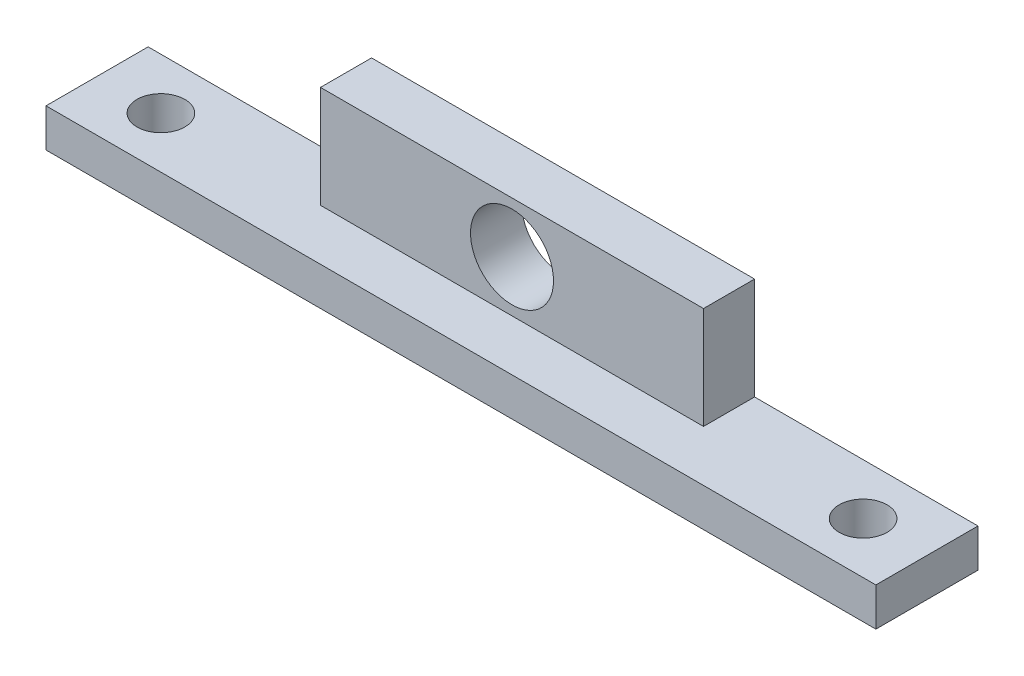
SolidWorks part; units mm, degrees
ref_plane "Front Plane" through (0, 0, 0) normal (0, 0, 1) x (1, 0, 0)
ref_plane "Top Plane" through (0, 0, 0) normal (0, 1, 0) x (1, 0, 0)
ref_plane "Right Plane" through (0, 0, 0) normal (1, 0, 0) x (0, 0, -1)
sketch "Sketch2" plane through (0, 0, 0) normal (0, 1, 0) x (1, 0, 0)
  line L0 (-27.5, 0) -> (27.5, 0) construction
  line L5 (-32.5, -4) -> (32.5, -4)
  line L6 (-32.5, -4) -> (-32.5, 4)
  line L7 (-32.5, 4) -> (32.5, 4)
  line L8 (32.5, -4) -> (32.5, 4)
  line L9 (-32.5, -4) -> (32.5, 4) construction
  line L10 (-32.5, 4) -> (32.5, -4) construction
  circle A0 centre (-27.5, 0) radius 1.875
  circle A1 centre (27.5, 0) radius 1.875
  point P0 (0, 0)
  point P10 (0, 0)
  dimension "D4" = 3.75
  dimension "D1" = 8
  dimension "D2" = 65
  dimension "D3" = 55
extrude "Boss-Extrude1" add sketch "Sketch2" along normal blind 3
sketch "Sketch4" plane through (0, 0, 0) normal (0, 0, 1) x (1, 0, 0)
  line L0 (-32.5, 3) -> (32.5, 3) construction
  line L1 (-15, 3) -> (15, 3)
  line L2 (-15, 3) -> (-15, 11)
  line L3 (-15, 11) -> (15, 11)
  line L4 (15, 3) -> (15, 11)
  circle A0 centre (0, 7) radius 3.25
  point P6 (0, 3)
  point P10 (0, 0)
  point P11 (-15, 7)
  point P12 (3.5929, 7)
  dimension "D2" = 6.5
  dimension "D1" = 8
  dimension "D3" = 30
extrude "Boss-Extrude2" add sketch "Sketch4" against normal up to surface (4 mm away) up to face at (0, 1.5, -4)
